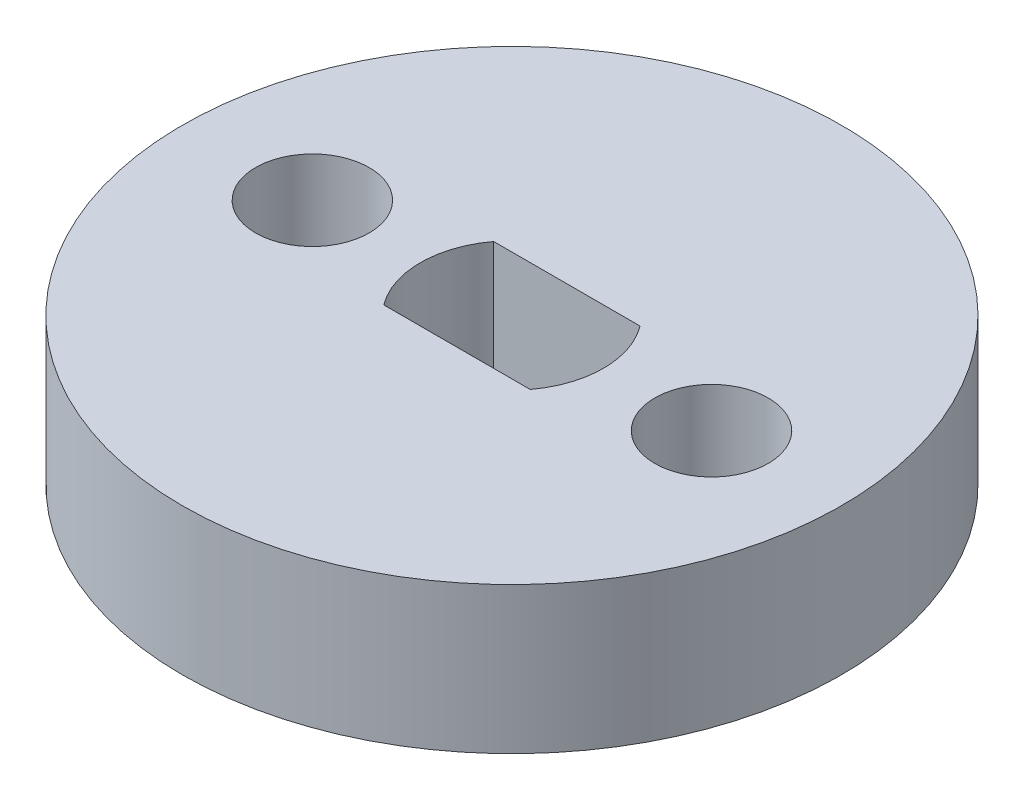
SolidWorks part; units mm, degrees
ref_plane "Front Plane" through (0, 0, 0) normal (0, 0, 1) x (1, 0, 0)
ref_plane "Top Plane" through (0, 0, 0) normal (0, 1, 0) x (1, 0, 0)
ref_plane "Right Plane" through (0, 0, 0) normal (1, 0, 0) x (0, 0, -1)
sketch "Sketch1" plane through (0, 0, 0) normal (0, 1, 0) x (1, 0, 0)
  circle A0 centre (0, 0) radius 9
  dimension "D1" = 18
base flange "Base-Flange1" sketch "Sketch1" thickness 4 reverse thickness direction no parameters "D1"=2
sketch "Sketch6" plane through (0, 0, 0) normal (0, 1, 0) x (1, 0, 0)
  line L1 (-2, 1.5) -> (2, 1.5)
  line L3 (0, -1.5) -> (2, -1.5)
  line L4 (0, -1.5) -> (-2, -1.5)
  arc A0 (-2, 1.5) -> (-2, -1.5) centre (0, 0) ccw
  arc A1 (2, -1.5) -> (2, 1.5) centre (0, 0) ccw
  point P7 (0, 1.5)
  dimension "D1" = 5
  dimension "D2" = 4
  dimension "D3" = 4
  dimension "D4" = 3
extrude "Cut-Extrude1" cut sketch "Sketch6" against normal blind 10 normal cut yes
sketch "Sketch7" plane through (0, 0, 0) normal (0, 1, 0) x (1, 0, 0)
  line L0 (-5.45, 0) -> (5.45, 0) construction
  line L1 (-7, 0) -> (-9, 0) construction
  line L2 (7, 0) -> (9, 0) construction
  circle A0 centre (-5.45, 0) radius 1.55
  circle A1 centre (5.45, 0) radius 1.55
  circle A3 centre (0, 0) radius 9 construction
  point P4 (0, 0)
  dimension "D1" = 3.1
  dimension "D2" = 2
extrude "Cut-Extrude2" cut sketch "Sketch7" against normal blind 10 normal cut yes
sketch "Bend-Lines1" [suppressed] plane through (0, 0, 0) normal (0, 1, 0) x (1, 0, 0)
sketch "Bounding-Box1" [suppressed] plane through (0, 0, 0) normal (0, 1, 0) x (1, 0, 0)
sheet metal parameters "Sheet-Metal1" thickness 4 parameters "D1"=2
flat pattern "Flat-Pattern1" [suppressed]
sketch "Bend-Lines2" plane through (0, 0, 0) normal (0, 1, 0) x (1, 0, 0)
sketch "Bounding-Box2" [suppressed] plane through (0, 0, 0) normal (0, 1, 0) x (1, 0, 0)
sheet metal parameters "Sheet-Metal2" thickness 4 parameters "D1"=2
flat pattern "Flat-Pattern1"
sketch "Bend-Lines2" plane through (0, 0, 0) normal (0, 1, 0) x (1, 0, 0)
sketch "Bounding-Box2" [suppressed] plane through (0, 0, 0) normal (0, 1, 0) x (1, 0, 0)
sheet metal parameters "Sheet-Metal3" thickness 4 parameters "D1"=2
flat pattern "Flat-Pattern1"
sketch "Bend-Lines2" plane through (0, 0, 0) normal (0, 1, 0) x (1, 0, 0)
sketch3d "Bounding-Box2" [suppressed]
  line L0 (-9.0385, 8.9612, 0) -> (-8.9611, -9.0386, 0) construction
  line L1 (8.9612, 9.0386, 0) -> (9.0386, -8.9611, 0) construction
  line L2 (-9.0385, 8.9612, 0) -> (8.9612, 9.0386, 0) construction
  line L3 (-8.9611, -9.0386, 0) -> (9.0386, -8.9611, 0) construction
